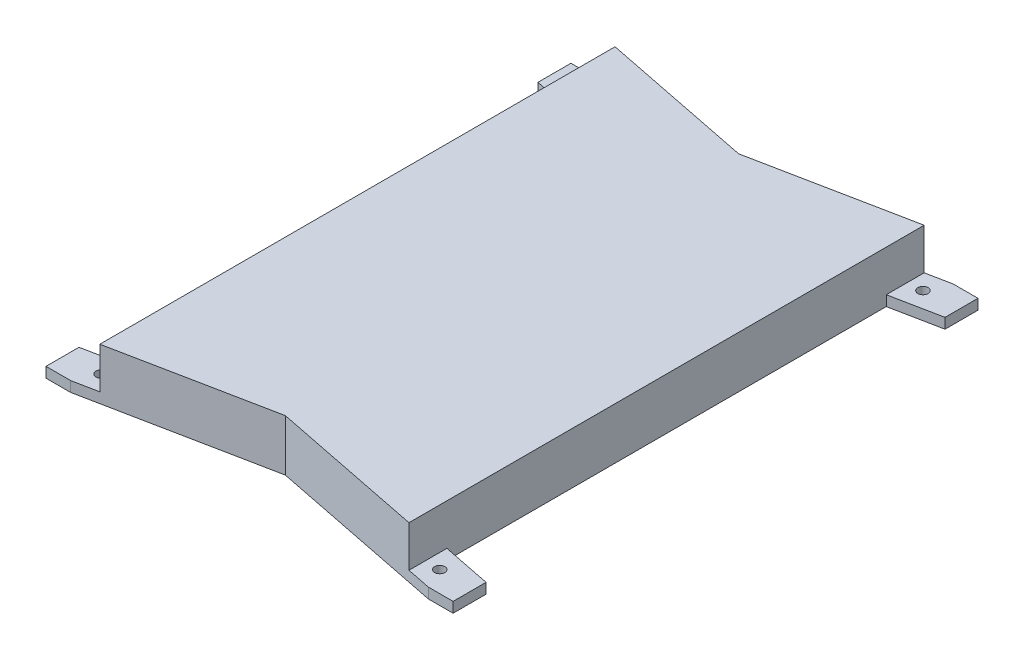
SolidWorks part; units mm, degrees
material "ABS"
ref_plane "Front Plane" through (0, 0, 0) normal (0, 0, 1) x (1, 0, 0)
ref_plane "Top Plane" through (0, 0, 0) normal (0, 1, 0) x (1, 0, 0)
ref_plane "Right Plane" through (0, 0, 0) normal (1, 0, 0) x (0, 0, -1)
ref_axis "X" through (-88.99, 0, 0) along (1, 0, 0)
ref_axis "Y" through (0, 55, 0) along (0, -1, 0)
ref_axis "Z" through (0, 0, -88.99) along (0, 0, 1)
sketch "Sketch1" plane through (0, 0, 0) normal (0, 1, 0) x (1, 0, 0)
  line L0 (-75, 106.6) -> (-75, -106.6)
  line L1 (-75, -125) -> (0, -110)
  line L2 (0, -110) -> (75, -125)
  line L3 (75, -106.6) -> (75, 106.6)
  line L4 (75, 125) -> (0, 110)
  line L5 (0, 110) -> (-75, 125)
  line L6 (0, 110) -> (0, -110) construction
  line L7 (-75, 0) -> (75, 0) construction
  line L8 (75, -125) -> (86.767, -127.3534)
  line L9 (86.767, -127.3534) -> (98.767, -127.3534)
  line L10 (98.767, -127.3534) -> (98.767, -111.3534)
  line L11 (98.767, -111.3534) -> (75, -106.6)
  line L12 (98.767, 111.3534) -> (75, 106.6)
  line L13 (98.767, 127.3534) -> (98.767, 111.3534)
  line L14 (86.767, 127.3534) -> (98.767, 127.3534)
  line L15 (75, 125) -> (86.767, 127.3534)
  line L16 (-98.767, -127.3534) -> (-98.767, -111.3534)
  line L17 (-86.767, -127.3534) -> (-98.767, -127.3534)
  line L18 (-75, -125) -> (-86.767, -127.3534)
  line L19 (-98.767, -111.3534) -> (-75, -106.6)
  line L20 (-98.767, 111.3534) -> (-75, 106.6)
  line L21 (-98.767, 127.3534) -> (-98.767, 111.3534)
  line L22 (-86.767, 127.3534) -> (-98.767, 127.3534)
  line L23 (-75, 125) -> (-86.767, 127.3534)
  line L24 (-75, 125) -> (-75, 106.6) construction
  line L25 (75, 125) -> (75, 106.6) construction
  line L26 (75, -106.6) -> (75, -125) construction
  line L27 (-75, -106.6) -> (-75, -125) construction
  dimension "D1" = 250
  dimension "D2" = 220
  dimension "D3" = 150
  dimension "D4" = 12
  dimension "D5" = 16
  dimension "D6" = 12
extrude "Boss-Extrude1" add sketch "Sketch1" along normal blind 5
sketch "Sketch3" plane through (0, 5, 0) normal (0, 1, 0) x (1, 0, 0)
  line L0 (-75, 106.6) -> (-75, 125) construction
  line L1 (0, 110) -> (-86.767, 127.3534) construction
  line L2 (75, 106.6) -> (75, 125) construction
  line L3 (86.767, 127.3534) -> (0, 110) construction
  line L4 (-75, -106.6) -> (-75, -125) construction
  line L5 (-86.767, -127.3534) -> (0, -110) construction
  line L6 (75, -106.6) -> (75, -125) construction
  line L7 (0, -110) -> (86.767, -127.3534) construction
  line L8 (-75, 106.6) -> (-75, -106.6) construction
  line L9 (75, -106.6) -> (75, 106.6) construction
  line L10 (75, 125) -> (0, 110)
  line L11 (0, 110) -> (-75, 125)
  line L12 (75, -106.6) -> (75, 106.6)
  line L13 (0, -110) -> (75, -125)
  line L14 (-75, 106.6) -> (-75, -106.6)
  line L15 (-75, -125) -> (0, -110)
  line L16 (-73, -122.5604) -> (0, -107.9604)
  line L17 (0, -107.9604) -> (73, -122.5604)
  line L18 (73, -106.6) -> (73, -122.5604)
  line L19 (73, -106.6) -> (73, 106.6)
  line L20 (73, 106.6) -> (73, 122.5604)
  line L21 (73, 122.5604) -> (0, 107.9604)
  line L22 (0, 107.9604) -> (-73, 122.5604)
  line L23 (-73, 106.6) -> (-73, 122.5604)
  line L24 (-73, 106.6) -> (-73, -106.6)
  line L25 (-73, -106.6) -> (-73, -122.5604)
  line L26 (75, 0) -> (-75, 0) construction
  line L27 (0, -110) -> (0, 110) construction
  line L28 (80.4076, -126.0815) -> (83.9461, -108.3892) construction
  line L29 (98.767, -111.3534) -> (75, -106.6) construction
  circle A0 centre (82.1768, -117.2354) radius 2.5
  circle A1 centre (-82.1768, -117.2354) radius 2.5
  circle A2 centre (-82.1768, 117.2354) radius 2.5
  circle A3 centre (82.1768, 117.2354) radius 2.5
  dimension "D2" = 5
  dimension "D3" = 82
  dimension "D1" = 2
extrude "Cut-Extrude1" cut sketch "Sketch3" against normal through all contours L24 L25 L16 L17 L18 L19 L20 L21 L22 L23 | A1 | A0 | A2 | A3 region at (0, 5, 0) region at (82.1768, 5, 117.2354) region at (-82.1768, 5, 117.2354) region at (-82.1768, 5, -117.2354) region at (82.1768, 5, -117.2354)
sketch "Sketch4" plane through (0, 5, 0) normal (0, 1, 0) x (1, 0, 0)
  line L0 (0, -107.9604) -> (73, -122.5604) construction
  line L1 (-73, -122.5604) -> (0, -107.9604) construction
  line L2 (73, 122.5604) -> (73, -122.5604) construction
  line L3 (73, 122.5604) -> (0, 107.9604) construction
  line L4 (0, 107.9604) -> (-73, 122.5604) construction
  line L5 (-73, 122.5604) -> (-73, -122.5604) construction
  line L6 (0, -107.9604) -> (73, -122.5604)
  line L7 (-73, -122.5604) -> (0, -107.9604)
  line L8 (73, 122.5604) -> (73, -122.5604)
  line L9 (73, 122.5604) -> (0, 107.9604)
  line L10 (0, 107.9604) -> (-73, 122.5604)
  line L11 (-73, 122.5604) -> (-73, -122.5604)
  line L12 (-75, 125) -> (-75, -125)
  line L13 (-75, -125) -> (0, -110)
  line L14 (0, -110) -> (75, -125)
  line L15 (75, 125) -> (75, -125)
  line L16 (75, 125) -> (0, 110)
  line L17 (0, 110) -> (-75, 125)
  dimension "D1" = 2
extrude "Boss-Extrude2" add sketch "Sketch4" along normal blind 20
sketch "Sketch5" plane through (0, 25, 0) normal (0, 1, 0) x (1, 0, 0)
  line L0 (75, 125) -> (0, 110) construction
  line L1 (0, 110) -> (-75, 125) construction
  line L2 (-75, 125) -> (-75, -125) construction
  line L3 (-75, -125) -> (0, -110) construction
  line L4 (0, -110) -> (75, -125) construction
  line L5 (75, -125) -> (75, 125) construction
  line L6 (75, 125) -> (0, 110)
  line L7 (0, 110) -> (-75, 125)
  line L8 (-75, 125) -> (-75, -125)
  line L9 (-75, -125) -> (0, -110)
  line L10 (0, -110) -> (75, -125)
  line L11 (75, -125) -> (75, 125)
extrude "Boss-Extrude3" add sketch "Sketch5" against normal blind 5
